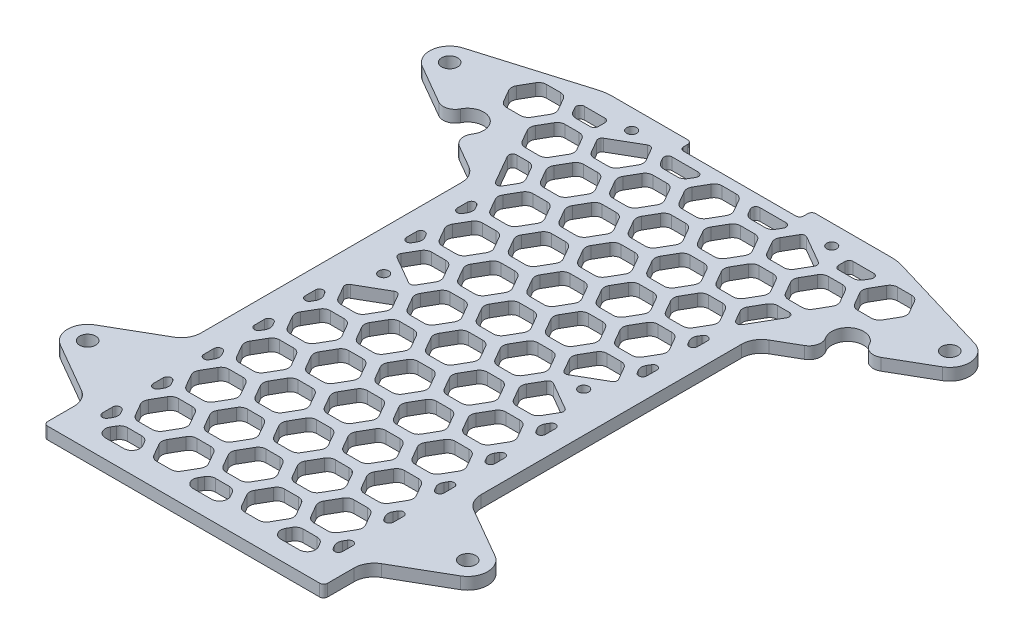
SolidWorks part; units mm, degrees
material "Thornel Mat VMA"
ref_plane "前视基准面" through (0, 0, 0) normal (0, 0, 1) x (1, 0, 0)
ref_plane "上视基准面" through (0, 0, 0) normal (0, 1, 0) x (1, 0, 0)
ref_plane "右视基准面" through (0, 0, 0) normal (1, 0, 0) x (0, 0, -1)
sketch "草图2" plane through (0, 0, 0) normal (0, 1, 0) x (1, 0, 0)
  line L0 (-43.1514, -24.9444) -> (-37.5, -28.2073)
  line L1 (35, -129.3771) -> (35, -137)
  line L3 (-47.5, -113.5) -> (-47.5, -18.5) construction
  line L6 (-37.8634, 4.5813) -> (-63.9317, -3.2094)
  line L7 (50, -117.8301) -> (37.5, -125.047)
  line L8 (37.5, -101.953) -> (50, -109.1699)
  line L11 (35, -32.5374) -> (35, -97.6229)
  line L14 (0, -55) -> (0, 55) construction
  line L16 (-35, 5) -> (35, 5)
  line L20 (43.1514, -24.9444) -> (37.5, -28.2073)
  line L23 (65, -12.3301) -> (55.2553, -17.9562)
  line L25 (-25, 0) -> (25, 0) construction
  line L26 (-25, 0) -> (-25, -62) construction
  line L27 (-25, -62) -> (25, -62) construction
  line L28 (25, 0) -> (25, -62) construction
  line L29 (-35, -129.3771) -> (-35, -137)
  line L30 (-35, -137) -> (35, -137)
  line L32 (-65, -12.3301) -> (-55.2553, -17.9562)
  line L33 (-35, -32.5374) -> (-35, -97.6229)
  line L34 (-37.5, -101.953) -> (-50, -109.1699)
  line L35 (-50, -117.8301) -> (-37.5, -125.047)
  line L36 (37.8634, 4.5813) -> (63.9317, -3.2094)
  arc A10 (-44.158, -20.6979) -> (-51.0745, -16.7047) centre (-47.5, -18.5) ccw
  circle A45 centre (-25, 0) radius 1.25
  circle A46 centre (-47.5, -43.5) radius 4 construction
  circle A47 centre (-62.5, -8) radius 2
  circle A49 centre (62.5, -8) radius 2
  circle A51 centre (47.5, -43.5) radius 4 construction
  circle A52 centre (25, 0) radius 1.25
  circle A53 centre (-25, -62) radius 1.25
  circle A54 centre (25, -62) radius 1.25
  arc A58 (-35, 5) -> (-37.8634, 4.5813) centre (-35, -5) ccw
  circle A59 centre (-47.5, -113.5) radius 2
  arc A60 (-50, -109.1699) -> (-50, -117.8301) centre (-47.5, -113.5) ccw
  arc A61 (-63.9317, -3.2094) -> (-65, -12.3301) centre (-62.5, -8) ccw
  arc A62 (-43.1514, -24.9444) -> (-44.158, -20.6979) centre (-41.6514, -22.3463) cw
  arc A63 (-51.0745, -16.7047) -> (-55.2553, -17.9562) centre (-53.7553, -15.3582) cw
  arc A64 (-35, -129.3771) -> (-37.5, -125.047) centre (-40, -129.3771) ccw
  arc A65 (-35, -97.6229) -> (-37.5, -101.953) centre (-40, -97.6229) cw
  arc A66 (-37.5, -28.2073) -> (-35, -32.5374) centre (-40, -32.5374) cw
  arc A67 (35, -129.3771) -> (37.5, -125.047) centre (40, -129.3771) cw
  circle A68 centre (47.5, -113.5) radius 2
  arc A69 (50, -109.1699) -> (50, -117.8301) centre (47.5, -113.5) cw
  arc A70 (35, -97.6229) -> (37.5, -101.953) centre (40, -97.6229) ccw
  arc A71 (37.5, -28.2073) -> (35, -32.5374) centre (40, -32.5374) ccw
  arc A72 (43.1514, -24.9444) -> (44.158, -20.6979) centre (41.6514, -22.3463) ccw
  arc A73 (44.158, -20.6979) -> (51.0745, -16.7047) centre (47.5, -18.5) cw
  arc A74 (51.0745, -16.7047) -> (55.2553, -17.9562) centre (53.7553, -15.3582) ccw
  arc A75 (63.9317, -3.2094) -> (65, -12.3301) centre (62.5, -8) cw
  arc A76 (35, 5) -> (37.8634, 4.5813) centre (35, -5) cw
  point P2 (36.4469, 55.8948)
  point P6 (0, 0)
  point P14 (-47.5, -63.0375)
  point P23 (0, 0)
  point P29 (-61.5336, 43)
  point P31 (-35, 38)
  point P32 (-35, 56)
  point P35 (-35.1257, 55.5775)
  point P36 (0, 0)
  point P37 (-47.5, 7.5)
  point P38 (-47.5, -61.5952)
  point P39 (32.0288, -82)
  point P41 (-35, -71.4625)
  point P42 (-35, 12.0845)
  point P44 (-35, 26.8228)
  dimension "D3" = 10
  dimension "D4" = 25
  dimension "D7" = 5
  dimension "D8" = 125
  dimension "D9" = 8
  dimension "D10" = 2.5
  dimension "D11" = 5
  dimension "D6" = 4
  dimension "D19" = 120
  dimension "D20" = 3
  dimension "D21" = 62
  dimension "D22" = 50
  dimension "D23" = 5
  dimension "D13" = 15
  dimension "D14" = 10.5
  dimension "D12" = 70
  dimension "D15" = 10
  dimension "D16" = 75
  dimension "D17" = 120
  dimension "D18" = 120
  dimension "D5" = 8
extrude "凸台-拉伸1" add sketch "草图2" along normal blind 3
sketch "草图5" plane through (0, 3, 0) normal (0, 1, 0) x (1, 0, 0)
  line L0 (2.8868, -10.6667) -> (2.8868, -13.3333) construction
  line L26 (-19.0526, -13.3333) -> (-24.8261, -13.3333)
  line L29 (-24.8261, -13.3333) -> (-27.7128, -18.3333)
  line L34 (-27.7128, -18.3333) -> (-24.8261, -23.3333)
  line L35 (-24.8261, -23.3333) -> (-19.0526, -23.3333)
  line L47 (35, 5) -> (-35, 5) construction
  line L60 (-19.0526, -23.3333) -> (-16.1658, -18.3333)
  line L61 (-16.1658, -18.3333) -> (-19.0526, -13.3333)
  line L65 (-30.0222, -19.6667) -> (-35.7957, -19.6667)
  line L104 (0, 0) -> (0, 5) construction
  line L105 (-25, 0) -> (25, -62) construction
  line L109 (-10.9697, -12) -> (-10.9697, -24.6667) construction
  line L113 (-15, 5) -> (15, 5)
  line L114 (-15, 5) -> (-15, 2)
  line L115 (-15, 2) -> (15, 2)
  line L116 (15, 5) -> (15, 2)
  line L122 (2.8868, -13.3333) -> (-2.8868, -13.3333)
  line L123 (-2.8868, -13.3333) -> (-5.7735, -18.3333)
  line L124 (-5.7735, -18.3333) -> (-2.8868, -23.3333)
  line L125 (-2.8868, -23.3333) -> (2.8868, -23.3333)
  line L126 (2.8868, -23.3333) -> (5.7735, -18.3333)
  line L127 (5.7735, -18.3333) -> (2.8868, -13.3333)
  line L128 (-8.0829, -19.6667) -> (-13.8564, -19.6667)
  line L129 (-13.8564, -19.6667) -> (-16.7432, -24.6667)
  line L130 (-16.7432, -24.6667) -> (-13.8564, -29.6667)
  line L131 (-13.8564, -29.6667) -> (-8.0829, -29.6667)
  line L132 (-8.0829, -29.6667) -> (-5.1962, -24.6667)
  line L133 (-5.1962, -24.6667) -> (-8.0829, -19.6667)
  line L134 (-8.0829, -7) -> (-13.8564, -7)
  line L135 (-13.8564, -7) -> (-16.7432, -12)
  line L136 (-16.7432, -12) -> (-13.8564, -17)
  line L137 (-13.8564, -17) -> (-8.0829, -17)
  line L138 (-8.0829, -17) -> (-5.1962, -12)
  line L139 (-5.1962, -12) -> (-8.0829, -7)
  line L140 (-10.9697, -24.6667) -> (0, -31) construction
  line L141 (0, -31) -> (0, -18.3333) construction
  line L142 (0, -18.3333) -> (-10.9697, -24.6667) construction
  line L143 (0, -5.6667) -> (0, -18.3333) construction
  line L144 (2.8868, -0.6667) -> (-2.8868, -0.6667)
  line L145 (-2.8868, -0.6667) -> (-5.7735, -5.6667)
  line L146 (-5.7735, -5.6667) -> (-2.8868, -10.6667)
  line L147 (-2.8868, -10.6667) -> (2.8868, -10.6667)
  line L148 (2.8868, -10.6667) -> (5.7735, -5.6667)
  line L149 (5.7735, -5.6667) -> (2.8868, -0.6667)
  line L151 (2.8868, -0.6667) -> (2.8868, 2) construction
  line L153 (-30.0222, -29.6667) -> (-27.1355, -24.6667)
  line L154 (-27.1355, -24.6667) -> (-30.0222, -19.6667)
  line L155 (-30.0222, -7) -> (-35.7957, -7)
  line L156 (-35.7957, -7) -> (-38.6825, -12)
  line L157 (-38.6825, -12) -> (-35.7957, -17)
  line L158 (-35.7957, -17) -> (-30.0222, -17)
  line L159 (-30.0222, -17) -> (-27.1355, -12)
  line L160 (-27.1355, -12) -> (-30.0222, -7)
  line L163 (-27.7128, -5.6667) -> (-24.8261, -10.6667)
  line L164 (-24.8261, -10.6667) -> (-19.0526, -10.6667)
  line L165 (-19.0526, -10.6667) -> (-16.1658, -5.6667)
  line L166 (-16.1658, -5.6667) -> (-19.0526, -0.6667)
  line L185 (-40.9919, -0.6667) -> (-46.7654, -0.6667)
  line L186 (-46.7654, -0.6667) -> (-49.6521, -5.6667)
  line L187 (-49.6521, -5.6667) -> (-46.7654, -10.6667)
  line L188 (-46.7654, -10.6667) -> (-40.9919, -10.6667)
  line L189 (-40.9919, -10.6667) -> (-38.1051, -5.6667)
  line L190 (-38.1051, -5.6667) -> (-40.9919, -0.6667)
  line L191 (-19.0526, -38.6667) -> (-24.8261, -38.6667)
  line L192 (-24.8261, -38.6667) -> (-27.7128, -43.6667)
  line L193 (-27.7128, -43.6667) -> (-24.8261, -48.6667)
  line L194 (-24.8261, -48.6667) -> (-19.0526, -48.6667)
  line L195 (-19.0526, -48.6667) -> (-16.1658, -43.6667)
  line L196 (-16.1658, -43.6667) -> (-19.0526, -38.6667)
  line L201 (-30.0222, -55) -> (-27.1355, -50)
  line L202 (-27.1355, -50) -> (-30.0222, -45)
  line L207 (-30.0222, -42.3333) -> (-27.1355, -37.3333)
  line L208 (-27.1355, -37.3333) -> (-30.0222, -32.3333)
  line L209 (-19.0526, -26) -> (-24.8261, -26)
  line L210 (-24.8261, -26) -> (-27.7128, -31)
  line L211 (-27.7128, -31) -> (-24.8261, -36)
  line L212 (-24.8261, -36) -> (-19.0526, -36)
  line L213 (-19.0526, -36) -> (-16.1658, -31)
  line L214 (-16.1658, -31) -> (-19.0526, -26)
  line L241 (-27.7128, -69) -> (-24.8261, -74)
  line L242 (-24.8261, -74) -> (-19.0526, -74)
  line L243 (-19.0526, -74) -> (-16.1658, -69)
  line L244 (-16.1658, -69) -> (-19.0526, -64)
  line L249 (-30.0222, -80.3333) -> (-27.1355, -75.3333)
  line L250 (-27.1355, -75.3333) -> (-30.0222, -70.3333)
  line L257 (-19.0526, -51.3333) -> (-24.8261, -51.3333)
  line L258 (-24.8261, -51.3333) -> (-27.7128, -56.3333)
  line L261 (-19.0526, -61.3333) -> (-16.1658, -56.3333)
  line L262 (-16.1658, -56.3333) -> (-19.0526, -51.3333)
  line L287 (-19.0526, -89.3333) -> (-24.8261, -89.3333)
  line L288 (-24.8261, -89.3333) -> (-27.7128, -94.3333)
  line L289 (-27.7128, -94.3333) -> (-24.8261, -99.3333)
  line L290 (-24.8261, -99.3333) -> (-19.0526, -99.3333)
  line L291 (-19.0526, -99.3333) -> (-16.1658, -94.3333)
  line L292 (-16.1658, -94.3333) -> (-19.0526, -89.3333)
  line L297 (-30.0222, -105.6667) -> (-27.1355, -100.6667)
  line L298 (-27.1355, -100.6667) -> (-30.0222, -95.6667)
  line L303 (-30.0222, -93) -> (-27.1355, -88)
  line L304 (-27.1355, -88) -> (-30.0222, -83)
  line L305 (-19.0526, -76.6667) -> (-24.8261, -76.6667)
  line L306 (-24.8261, -76.6667) -> (-27.7128, -81.6667)
  line L307 (-27.7128, -81.6667) -> (-24.8261, -86.6667)
  line L308 (-24.8261, -86.6667) -> (-19.0526, -86.6667)
  line L309 (-19.0526, -86.6667) -> (-16.1658, -81.6667)
  line L310 (-16.1658, -81.6667) -> (-19.0526, -76.6667)
  line L335 (-19.0526, -114.6667) -> (-24.8261, -114.6667)
  line L336 (-24.8261, -114.6667) -> (-27.7128, -119.6667)
  line L337 (-27.7128, -119.6667) -> (-24.8261, -124.6667)
  line L338 (-24.8261, -124.6667) -> (-19.0526, -124.6667)
  line L339 (-19.0526, -124.6667) -> (-16.1658, -119.6667)
  line L340 (-16.1658, -119.6667) -> (-19.0526, -114.6667)
  line L345 (-30.0222, -131) -> (-27.1355, -126)
  line L346 (-27.1355, -126) -> (-30.0222, -121)
  line L351 (-30.0222, -118.3333) -> (-27.1355, -113.3333)
  line L352 (-27.1355, -113.3333) -> (-30.0222, -108.3333)
  line L353 (-19.0526, -102) -> (-24.8261, -102)
  line L354 (-24.8261, -102) -> (-27.7128, -107)
  line L355 (-27.7128, -107) -> (-24.8261, -112)
  line L356 (-24.8261, -112) -> (-19.0526, -112)
  line L357 (-19.0526, -112) -> (-16.1658, -107)
  line L358 (-16.1658, -107) -> (-19.0526, -102)
  line L401 (-19.0526, -127.3333) -> (-24.8261, -127.3333)
  line L402 (-24.8261, -127.3333) -> (-27.7128, -132.3333)
  line L406 (-16.1658, -132.3333) -> (-19.0526, -127.3333)
  line L431 (2.8868, -38.6667) -> (-2.8868, -38.6667)
  line L432 (-2.8868, -38.6667) -> (-5.7735, -43.6667)
  line L433 (-5.7735, -43.6667) -> (-2.8868, -48.6667)
  line L434 (-2.8868, -48.6667) -> (2.8868, -48.6667)
  line L435 (2.8868, -48.6667) -> (5.7735, -43.6667)
  line L436 (5.7735, -43.6667) -> (2.8868, -38.6667)
  line L437 (-8.0829, -45) -> (-13.8564, -45)
  line L438 (-13.8564, -45) -> (-16.7432, -50)
  line L439 (-16.7432, -50) -> (-13.8564, -55)
  line L440 (-13.8564, -55) -> (-8.0829, -55)
  line L441 (-8.0829, -55) -> (-5.1962, -50)
  line L442 (-5.1962, -50) -> (-8.0829, -45)
  line L443 (-8.0829, -32.3333) -> (-13.8564, -32.3333)
  line L444 (-13.8564, -32.3333) -> (-16.7432, -37.3333)
  line L445 (-16.7432, -37.3333) -> (-13.8564, -42.3333)
  line L446 (-13.8564, -42.3333) -> (-8.0829, -42.3333)
  line L447 (-8.0829, -42.3333) -> (-5.1962, -37.3333)
  line L448 (-5.1962, -37.3333) -> (-8.0829, -32.3333)
  line L449 (2.8868, -26) -> (-2.8868, -26)
  line L450 (-2.8868, -26) -> (-5.7735, -31)
  line L451 (-5.7735, -31) -> (-2.8868, -36)
  line L452 (-2.8868, -36) -> (2.8868, -36)
  line L453 (2.8868, -36) -> (5.7735, -31)
  line L454 (5.7735, -31) -> (2.8868, -26)
  line L455 (2.8868, -64) -> (-2.8868, -64)
  line L456 (-2.8868, -64) -> (-5.7735, -69)
  line L457 (-5.7735, -69) -> (-2.8868, -74)
  line L458 (-2.8868, -74) -> (2.8868, -74)
  line L459 (2.8868, -74) -> (5.7735, -69)
  line L460 (5.7735, -69) -> (2.8868, -64)
  line L461 (-8.0829, -70.3333) -> (-13.8564, -70.3333)
  line L462 (-13.8564, -70.3333) -> (-16.7432, -75.3333)
  line L463 (-16.7432, -75.3333) -> (-13.8564, -80.3333)
  line L464 (-13.8564, -80.3333) -> (-8.0829, -80.3333)
  line L465 (-8.0829, -80.3333) -> (-5.1962, -75.3333)
  line L466 (-5.1962, -75.3333) -> (-8.0829, -70.3333)
  line L467 (-8.0829, -57.6667) -> (-13.8564, -57.6667)
  line L468 (-13.8564, -57.6667) -> (-16.7432, -62.6667)
  line L469 (-16.7432, -62.6667) -> (-13.8564, -67.6667)
  line L470 (-13.8564, -67.6667) -> (-8.0829, -67.6667)
  line L471 (-8.0829, -67.6667) -> (-5.1962, -62.6667)
  line L472 (-5.1962, -62.6667) -> (-8.0829, -57.6667)
  line L473 (2.8868, -51.3333) -> (-2.8868, -51.3333)
  line L474 (-2.8868, -51.3333) -> (-5.7735, -56.3333)
  line L475 (-5.7735, -56.3333) -> (-2.8868, -61.3333)
  line L476 (-2.8868, -61.3333) -> (2.8868, -61.3333)
  line L477 (2.8868, -61.3333) -> (5.7735, -56.3333)
  line L478 (5.7735, -56.3333) -> (2.8868, -51.3333)
  line L479 (2.8868, -89.3333) -> (-2.8868, -89.3333)
  line L480 (-2.8868, -89.3333) -> (-5.7735, -94.3333)
  line L481 (-5.7735, -94.3333) -> (-2.8868, -99.3333)
  line L482 (-2.8868, -99.3333) -> (2.8868, -99.3333)
  line L483 (2.8868, -99.3333) -> (5.7735, -94.3333)
  line L484 (5.7735, -94.3333) -> (2.8868, -89.3333)
  line L485 (-8.0829, -95.6667) -> (-13.8564, -95.6667)
  line L486 (-13.8564, -95.6667) -> (-16.7432, -100.6667)
  line L487 (-16.7432, -100.6667) -> (-13.8564, -105.6667)
  line L488 (-13.8564, -105.6667) -> (-8.0829, -105.6667)
  line L489 (-8.0829, -105.6667) -> (-5.1962, -100.6667)
  line L490 (-5.1962, -100.6667) -> (-8.0829, -95.6667)
  line L491 (-8.0829, -83) -> (-13.8564, -83)
  line L492 (-13.8564, -83) -> (-16.7432, -88)
  line L493 (-16.7432, -88) -> (-13.8564, -93)
  line L494 (-13.8564, -93) -> (-8.0829, -93)
  line L495 (-8.0829, -93) -> (-5.1962, -88)
  line L496 (-5.1962, -88) -> (-8.0829, -83)
  line L497 (2.8868, -76.6667) -> (-2.8868, -76.6667)
  line L498 (-2.8868, -76.6667) -> (-5.7735, -81.6667)
  line L499 (-5.7735, -81.6667) -> (-2.8868, -86.6667)
  line L500 (-2.8868, -86.6667) -> (2.8868, -86.6667)
  line L501 (2.8868, -86.6667) -> (5.7735, -81.6667)
  line L502 (5.7735, -81.6667) -> (2.8868, -76.6667)
  line L503 (2.8868, -114.6667) -> (-2.8868, -114.6667)
  line L504 (-2.8868, -114.6667) -> (-5.7735, -119.6667)
  line L505 (-5.7735, -119.6667) -> (-2.8868, -124.6667)
  line L506 (-2.8868, -124.6667) -> (2.8868, -124.6667)
  line L507 (2.8868, -124.6667) -> (5.7735, -119.6667)
  line L508 (5.7735, -119.6667) -> (2.8868, -114.6667)
  line L509 (-8.0829, -121) -> (-13.8564, -121)
  line L510 (-13.8564, -121) -> (-16.7432, -126)
  line L511 (-16.7432, -126) -> (-13.8564, -131)
  line L512 (-13.8564, -131) -> (-8.0829, -131)
  line L513 (-8.0829, -131) -> (-5.1962, -126)
  line L514 (-5.1962, -126) -> (-8.0829, -121)
  line L515 (-8.0829, -108.3333) -> (-13.8564, -108.3333)
  line L516 (-13.8564, -108.3333) -> (-16.7432, -113.3333)
  line L517 (-16.7432, -113.3333) -> (-13.8564, -118.3333)
  line L518 (-13.8564, -118.3333) -> (-8.0829, -118.3333)
  line L519 (-8.0829, -118.3333) -> (-5.1962, -113.3333)
  line L520 (-5.1962, -113.3333) -> (-8.0829, -108.3333)
  line L521 (2.8868, -102) -> (-2.8868, -102)
  line L522 (-2.8868, -102) -> (-5.7735, -107)
  line L523 (-5.7735, -107) -> (-2.8868, -112)
  line L524 (-2.8868, -112) -> (2.8868, -112)
  line L525 (2.8868, -112) -> (5.7735, -107)
  line L526 (5.7735, -107) -> (2.8868, -102)
  line L545 (2.8868, -127.3333) -> (-2.8868, -127.3333)
  line L546 (-2.8868, -127.3333) -> (-5.7735, -132.3333)
  line L550 (5.7735, -132.3333) -> (2.8868, -127.3333)
  line L551 (-10.9697, -12) -> (-21.9393, -18.3333) construction
  line L552 (-21.9393, -18.3333) -> (-10.9697, -24.6667) construction
  line L553 (-19.0526, -0.6667) -> (-27.7128, -5.6667)
  line L554 (-57.735, -55) -> (-51.9615, -55)
  line L555 (-40.9919, -64) -> (-46.7654, -64)
  line L556 (-46.7654, -64) -> (-49.6521, -69)
  line L557 (-49.6521, -69) -> (-46.7654, -74)
  line L558 (-46.7654, -74) -> (-40.9919, -74)
  line L559 (-40.9919, -74) -> (-38.1051, -69)
  line L560 (-38.1051, -69) -> (-40.9919, -64)
  line L561 (-51.9615, -70.3333) -> (-57.735, -70.3333)
  line L562 (-57.735, -70.3333) -> (-60.6218, -75.3333)
  line L563 (-60.6218, -75.3333) -> (-57.735, -80.3333)
  line L564 (-57.735, -80.3333) -> (-51.9615, -80.3333)
  line L565 (-51.9615, -80.3333) -> (-49.0748, -75.3333)
  line L566 (-49.0748, -75.3333) -> (-51.9615, -70.3333)
  line L567 (-51.9615, -57.6667) -> (-57.735, -57.6667)
  line L568 (-57.735, -57.6667) -> (-60.6218, -62.6667)
  line L569 (-60.6218, -62.6667) -> (-57.735, -67.6667)
  line L570 (-57.735, -67.6667) -> (-51.9615, -67.6667)
  line L571 (-51.9615, -67.6667) -> (-49.0748, -62.6667)
  line L572 (-49.0748, -62.6667) -> (-51.9615, -57.6667)
  line L573 (-49.6521, -56.3333) -> (-46.7654, -61.3333)
  line L574 (-46.7654, -61.3333) -> (-40.9919, -61.3333)
  line L575 (-40.9919, -61.3333) -> (-38.1051, -56.3333)
  line L576 (-40.9919, -89.3333) -> (-46.7654, -89.3333)
  line L577 (-46.7654, -89.3333) -> (-49.6521, -94.3333)
  line L578 (-49.6521, -94.3333) -> (-46.7654, -99.3333)
  line L579 (-46.7654, -99.3333) -> (-40.9919, -99.3333)
  line L580 (-40.9919, -99.3333) -> (-38.1051, -94.3333)
  line L581 (-38.1051, -94.3333) -> (-40.9919, -89.3333)
  line L582 (-51.9615, -95.6667) -> (-57.735, -95.6667)
  line L583 (-57.735, -95.6667) -> (-60.6218, -100.6667)
  line L584 (-60.6218, -100.6667) -> (-57.735, -105.6667)
  line L585 (-57.735, -105.6667) -> (-51.9615, -105.6667)
  line L586 (-51.9615, -105.6667) -> (-49.0748, -100.6667)
  line L587 (-49.0748, -100.6667) -> (-51.9615, -95.6667)
  line L588 (-51.9615, -83) -> (-57.735, -83)
  line L589 (-57.735, -83) -> (-60.6218, -88)
  line L590 (-60.6218, -88) -> (-57.735, -93)
  line L591 (-57.735, -93) -> (-51.9615, -93)
  line L592 (-51.9615, -93) -> (-49.0748, -88)
  line L593 (-49.0748, -88) -> (-51.9615, -83)
  line L594 (-40.9919, -76.6667) -> (-46.7654, -76.6667)
  line L595 (-46.7654, -76.6667) -> (-49.6521, -81.6667)
  line L596 (-49.6521, -81.6667) -> (-46.7654, -86.6667)
  line L597 (-46.7654, -86.6667) -> (-40.9919, -86.6667)
  line L598 (-40.9919, -86.6667) -> (-38.1051, -81.6667)
  line L599 (-38.1051, -81.6667) -> (-40.9919, -76.6667)
  line L600 (-40.9919, -114.6667) -> (-46.7654, -114.6667)
  line L601 (-46.7654, -114.6667) -> (-49.6521, -119.6667)
  line L602 (-49.6521, -119.6667) -> (-46.7654, -124.6667)
  line L603 (-46.7654, -124.6667) -> (-40.9919, -124.6667)
  line L604 (-40.9919, -124.6667) -> (-38.1051, -119.6667)
  line L605 (-38.1051, -119.6667) -> (-40.9919, -114.6667)
  line L606 (-51.9615, -121) -> (-57.735, -121)
  line L607 (-57.735, -121) -> (-60.6218, -126)
  line L608 (-60.6218, -126) -> (-57.735, -131)
  line L609 (-57.735, -131) -> (-51.9615, -131)
  line L610 (-51.9615, -131) -> (-49.0748, -126)
  line L611 (-49.0748, -126) -> (-51.9615, -121)
  line L612 (-51.9615, -108.3333) -> (-57.735, -108.3333)
  line L613 (-57.735, -108.3333) -> (-60.6218, -113.3333)
  line L614 (-60.6218, -113.3333) -> (-57.735, -118.3333)
  line L615 (-57.735, -118.3333) -> (-51.9615, -118.3333)
  line L616 (-51.9615, -118.3333) -> (-49.0748, -113.3333)
  line L617 (-49.0748, -113.3333) -> (-51.9615, -108.3333)
  line L618 (-40.9919, -102) -> (-46.7654, -102)
  line L619 (-46.7654, -102) -> (-49.6521, -107)
  line L620 (-49.6521, -107) -> (-46.7654, -112)
  line L621 (-46.7654, -112) -> (-40.9919, -112)
  line L622 (-40.9919, -112) -> (-38.1051, -107)
  line L623 (-38.1051, -107) -> (-40.9919, -102)
  line L624 (-40.9919, -140) -> (-46.7654, -140)
  line L625 (-46.7654, -140) -> (-49.6521, -145)
  line L626 (-49.6521, -145) -> (-46.7654, -150)
  line L627 (-46.7654, -150) -> (-40.9919, -150)
  line L628 (-40.9919, -150) -> (-38.1051, -145)
  line L629 (-38.1051, -145) -> (-40.9919, -140)
  line L630 (-51.9615, -146.3333) -> (-57.735, -146.3333)
  line L631 (-57.735, -146.3333) -> (-60.6218, -151.3333)
  line L632 (-60.6218, -151.3333) -> (-57.735, -156.3333)
  line L633 (-57.735, -156.3333) -> (-51.9615, -156.3333)
  line L634 (-51.9615, -156.3333) -> (-49.0748, -151.3333)
  line L635 (-49.0748, -151.3333) -> (-51.9615, -146.3333)
  line L636 (-51.9615, -133.6667) -> (-57.735, -133.6667)
  line L637 (-57.735, -133.6667) -> (-60.6218, -138.6667)
  line L638 (-60.6218, -138.6667) -> (-57.735, -143.6667)
  line L639 (-57.735, -143.6667) -> (-51.9615, -143.6667)
  line L640 (-51.9615, -143.6667) -> (-49.0748, -138.6667)
  line L641 (-49.0748, -138.6667) -> (-51.9615, -133.6667)
  line L642 (-40.9919, -127.3333) -> (-46.7654, -127.3333)
  line L643 (-46.7654, -127.3333) -> (-49.6521, -132.3333)
  line L644 (-49.6521, -132.3333) -> (-46.7654, -137.3333)
  line L645 (-46.7654, -137.3333) -> (-40.9919, -137.3333)
  line L646 (-40.9919, -137.3333) -> (-38.1051, -132.3333)
  line L647 (-38.1051, -132.3333) -> (-40.9919, -127.3333)
  line L648 (-40.9919, -13.3333) -> (-46.7654, -13.3333)
  line L649 (-46.7654, -13.3333) -> (-49.6521, -18.3333)
  line L650 (-49.6521, -18.3333) -> (-46.7654, -23.3333)
  line L651 (-46.7654, -23.3333) -> (-40.9919, -23.3333)
  line L652 (-40.9919, -23.3333) -> (-38.1051, -18.3333)
  line L653 (-38.1051, -18.3333) -> (-40.9919, -13.3333)
  line L654 (-51.9615, -19.6667) -> (-57.735, -19.6667)
  line L655 (-57.735, -19.6667) -> (-60.6218, -24.6667)
  line L656 (-60.6218, -24.6667) -> (-57.735, -29.6667)
  line L657 (-57.735, -29.6667) -> (-51.9615, -29.6667)
  line L658 (-51.9615, -29.6667) -> (-49.0748, -24.6667)
  line L659 (-49.0748, -24.6667) -> (-51.9615, -19.6667)
  line L660 (-60.6218, -12) -> (-57.735, -17)
  line L661 (-57.735, -17) -> (-51.9615, -17)
  line L662 (-51.9615, -17) -> (-49.0748, -12)
  line L663 (-40.9919, -38.6667) -> (-46.7654, -38.6667)
  line L664 (-46.7654, -38.6667) -> (-49.6521, -43.6667)
  line L665 (-49.6521, -43.6667) -> (-46.7654, -48.6667)
  line L666 (-46.7654, -48.6667) -> (-40.9919, -48.6667)
  line L667 (-40.9919, -48.6667) -> (-38.1051, -43.6667)
  line L668 (-38.1051, -43.6667) -> (-40.9919, -38.6667)
  line L669 (-51.9615, -45) -> (-57.735, -45)
  line L670 (-57.735, -45) -> (-60.6218, -50)
  line L671 (-60.6218, -50) -> (-57.735, -55)
  line L672 (-51.9615, -55) -> (-49.0748, -50)
  line L673 (-49.0748, -50) -> (-51.9615, -45)
  line L674 (-51.9615, -32.3333) -> (-57.735, -32.3333)
  line L675 (-57.735, -32.3333) -> (-60.6218, -37.3333)
  line L676 (-60.6218, -37.3333) -> (-57.735, -42.3333)
  line L677 (-57.735, -42.3333) -> (-51.9615, -42.3333)
  line L678 (-51.9615, -42.3333) -> (-49.0748, -37.3333)
  line L679 (-49.0748, -37.3333) -> (-51.9615, -32.3333)
  line L680 (-40.9919, -26) -> (-46.7654, -26)
  line L681 (-46.7654, -26) -> (-49.6521, -31)
  line L682 (-49.6521, -31) -> (-46.7654, -36)
  line L683 (-46.7654, -36) -> (-40.9919, -36)
  line L684 (-40.9919, -36) -> (-38.1051, -31)
  line L685 (-38.1051, -31) -> (-40.9919, -26)
  line L686 (-40.9919, -51.3333) -> (-46.7654, -51.3333)
  line L687 (-46.7654, -51.3333) -> (-49.6521, -56.3333)
  line L688 (-38.1051, -56.3333) -> (-40.9919, -51.3333)
  line L689 (-51.9615, -7) -> (-57.735, -7)
  line L690 (-57.735, -7) -> (-60.6218, -12)
  line L691 (-49.0748, -12) -> (-51.9615, -7)
  line L692 (-15.9734, -0.6667) -> (-13.8564, -4.3333)
  line L693 (-13.8564, -4.3333) -> (-8.0829, -4.3333)
  line L694 (-8.0829, -4.3333) -> (-5.966, -0.6667)
  line L695 (-5.966, -0.6667) -> (-15.9734, -0.6667)
  line L696 (-8.0829, -4.3333) -> (-8.0829, -7) construction
  line L697 (-35.7957, -7) -> (-35.7957, -4.3333) construction
  line L698 (-19.0526, -0.6667) -> (-24.8261, -0.6667)
  line L699 (-24.8261, -0.6667) -> (-27.7128, -5.6667)
  line L700 (-37.9127, -0.6667) -> (-30.0222, -0.6667)
  line L701 (-37.9127, -0.6667) -> (-35.7957, -4.3333)
  line L702 (-35.7957, -4.3333) -> (-30.0222, -4.3333)
  line L703 (-30.0222, -0.6667) -> (-30.0222, -4.3333)
  line L704 (-35.7957, -19.6667) -> (-30.0222, -29.6667)
  line L705 (-35.7957, -19.6667) -> (-38.6825, -24.6667)
  line L706 (-38.6825, -24.6667) -> (-35.7957, -29.6667)
  line L707 (-35.7957, -29.6667) -> (-30.0222, -29.6667)
  line L708 (-30.0222, -45) -> (-35.7957, -45)
  line L709 (-35.7957, -45) -> (-38.6825, -50)
  line L710 (-38.6825, -50) -> (-35.7957, -55)
  line L711 (-35.7957, -55) -> (-30.0222, -55)
  line L712 (-30.0222, -32.3333) -> (-35.7957, -32.3333)
  line L713 (-35.7957, -32.3333) -> (-38.6825, -37.3333)
  line L714 (-38.6825, -37.3333) -> (-35.7957, -42.3333)
  line L715 (-35.7957, -42.3333) -> (-30.0222, -42.3333)
  line L716 (-30.0222, -70.3333) -> (-35.7957, -70.3333)
  line L717 (-35.7957, -70.3333) -> (-38.6825, -75.3333)
  line L718 (-38.6825, -75.3333) -> (-35.7957, -80.3333)
  line L719 (-35.7957, -80.3333) -> (-30.0222, -80.3333)
  line L720 (-30.0222, -57.6667) -> (-35.7957, -57.6667)
  line L721 (-35.7957, -57.6667) -> (-38.6825, -62.6667)
  line L722 (-38.6825, -62.6667) -> (-35.7957, -67.6667)
  line L723 (-35.7957, -67.6667) -> (-30.0222, -67.6667)
  line L724 (-30.0222, -95.6667) -> (-35.7957, -95.6667)
  line L725 (-35.7957, -95.6667) -> (-38.6825, -100.6667)
  line L726 (-38.6825, -100.6667) -> (-35.7957, -105.6667)
  line L727 (-35.7957, -105.6667) -> (-30.0222, -105.6667)
  line L728 (-30.0222, -83) -> (-35.7957, -83)
  line L729 (-35.7957, -83) -> (-38.6825, -88)
  line L730 (-38.6825, -88) -> (-35.7957, -93)
  line L731 (-35.7957, -93) -> (-30.0222, -93)
  line L732 (-30.0222, -121) -> (-35.7957, -121)
  line L733 (-35.7957, -121) -> (-38.6825, -126)
  line L734 (-38.6825, -126) -> (-35.7957, -131)
  line L735 (-35.7957, -131) -> (-30.0222, -131)
  line L736 (-30.0222, -108.3333) -> (-35.7957, -108.3333)
  line L737 (-35.7957, -108.3333) -> (-38.6825, -113.3333)
  line L738 (-38.6825, -113.3333) -> (-35.7957, -118.3333)
  line L739 (-35.7957, -118.3333) -> (-30.0222, -118.3333)
  line L740 (-30.0222, -146.3333) -> (-35.7957, -146.3333)
  line L741 (-35.7957, -146.3333) -> (-38.6825, -151.3333)
  line L742 (-38.6825, -151.3333) -> (-35.7957, -156.3333)
  line L743 (-35.7957, -156.3333) -> (-30.0222, -156.3333)
  line L744 (-30.0222, -133.6667) -> (-35.7957, -133.6667)
  line L745 (-35.7957, -133.6667) -> (-38.6825, -138.6667)
  line L746 (-38.6825, -138.6667) -> (-35.7957, -143.6667)
  line L747 (-35.7957, -143.6667) -> (-30.0222, -143.6667)
  line L748 (-19.0526, -140) -> (-24.8261, -140)
  line L749 (-24.8261, -140) -> (-27.7128, -145)
  line L750 (-27.7128, -145) -> (-24.8261, -150)
  line L751 (-24.8261, -150) -> (-19.0526, -150)
  line L752 (-19.0526, -150) -> (-16.1658, -145)
  line L753 (-16.1658, -145) -> (-19.0526, -140)
  line L754 (-30.0222, -156.3333) -> (-27.1355, -151.3333)
  line L755 (-27.1355, -151.3333) -> (-30.0222, -146.3333)
  line L756 (-30.0222, -143.6667) -> (-27.1355, -138.6667)
  line L757 (-27.1355, -138.6667) -> (-30.0222, -133.6667)
  line L758 (-27.7128, -132.3333) -> (-24.8261, -137.3333)
  line L759 (-24.8261, -137.3333) -> (-19.0526, -137.3333)
  line L760 (-19.0526, -137.3333) -> (-16.1658, -132.3333)
  line L761 (2.8868, -140) -> (-2.8868, -140)
  line L762 (-2.8868, -140) -> (-5.7735, -145)
  line L763 (-5.7735, -145) -> (-2.8868, -150)
  line L764 (-2.8868, -150) -> (2.8868, -150)
  line L765 (2.8868, -150) -> (5.7735, -145)
  line L766 (5.7735, -145) -> (2.8868, -140)
  line L767 (-8.0829, -146.3333) -> (-13.8564, -146.3333)
  line L768 (-13.8564, -146.3333) -> (-16.7432, -151.3333)
  line L769 (-16.7432, -151.3333) -> (-13.8564, -156.3333)
  line L770 (-13.8564, -156.3333) -> (-8.0829, -156.3333)
  line L771 (-8.0829, -156.3333) -> (-5.1962, -151.3333)
  line L772 (-5.1962, -151.3333) -> (-8.0829, -146.3333)
  line L773 (-13.8564, -133.6667) -> (-16.7432, -138.6667)
  line L774 (-16.7432, -138.6667) -> (-13.8564, -143.6667)
  line L775 (-13.8564, -143.6667) -> (-8.0829, -143.6667)
  line L776 (-8.0829, -143.6667) -> (-5.1962, -138.6667)
  line L777 (-5.1962, -138.6667) -> (-8.0829, -133.6667)
  line L778 (-5.7735, -132.3333) -> (-2.8868, -137.3333)
  line L779 (-2.8868, -137.3333) -> (2.8868, -137.3333)
  line L780 (2.8868, -137.3333) -> (5.7735, -132.3333)
  line L781 (-8.0829, -133.6667) -> (-13.8564, -133.6667)
  line L782 (-30.0222, -32.3333) -> (-30.0222, -42.3333)
  line L783 (-30.0222, -55) -> (-30.0222, -45)
  line L785 (-30.0222, -70.3333) -> (-30.0222, -80.3333)
  line L786 (-30.0222, -83) -> (-30.0222, -93)
  line L787 (-30.0222, -95.6667) -> (-30.0222, -105.6667)
  line L788 (-30.0222, -108.3333) -> (-30.0222, -118.3333)
  line L789 (-30.0222, -121) -> (-30.0222, -131)
  line L790 (-27.7128, -132.3333) -> (-16.1658, -132.3333)
  line L791 (-19.0526, -61.3333) -> (-27.7128, -56.3333)
  line L792 (-27.7128, -69) -> (-19.0526, -64)
  line L794 (5.7735, -132.3333) -> (-5.7735, -132.3333)
  line L796 (-24.8261, -61.3333) -> (-19.0526, -61.3333)
  line L797 (-27.7128, -56.3333) -> (-24.8261, -61.3333)
  line L798 (-19.0526, -64) -> (-24.8261, -64)
  line L799 (-24.8261, -64) -> (-27.7128, -69)
  line L800 (-30.0222, -67.6667) -> (-27.1355, -62.6667)
  line L801 (-27.1355, -62.6667) -> (-30.0222, -57.6667)
  circle A20 centre (0, -31) radius 5 construction
  circle A21 centre (-21.9393, -18.3333) radius 5 construction
  circle A22 centre (0, -18.3333) radius 5 construction
  circle A23 centre (-10.9697, -24.6667) radius 5 construction
  circle A24 centre (-10.9697, -12) radius 5 construction
  circle A25 centre (0, -5.6667) radius 5 construction
  dimension "D3" = 10
  dimension "D4" = 6
  dimension "D1" = 3
  dimension "D2" = 30
  dimension "D5" = 3
extrude "切除-拉伸4" cut sketch "草图5" against normal through all
mirror "镜向1" about plane through (0, 0, 0) normal (1, 0, 0) of "切除-拉伸4"
fillet "圆角2" radius 1 60 edges at (30.0222, 1.5, 32.3333) (30.0222, 1.5, 45) (30.0222, 1.5, 70.3333) (30.0222, 1.5, 83) (30.0222, 1.5, 95.6667) (30.0222, 1.5, 108.3333) (30.0222, 1.5, 121) (30.0222, 1.5, 131) (30.0222, 1.5, 118.3333) (30.0222, 1.5, 105.6667) (30.0222, 1.5, 93) (30.0222, 1.5, 80.3333) (30.0222, 1.5, 55) (30.0222, 1.5, 42.3333) (-30.0222, 1.5, 42.3333) (-30.0222, 1.5, 55) (-30.0222, 1.5, 80.3333) (-30.0222, 1.5, 93) (-30.0222, 1.5, 105.6667) (-30.0222, 1.5, 118.3333) (-30.0222, 1.5, 131) (-30.0222, 1.5, 121) (-30.0222, 1.5, 108.3333) (-30.0222, 1.5, 95.6667) (-30.0222, 1.5, 83) (-30.0222, 1.5, 70.3333) (-30.0222, 1.5, 45) (-30.0222, 1.5, 32.3333) (35.7957, 1.5, 19.6667) (30.0222, 1.5, 29.6667) (-35.7957, 1.5, 19.6667) (-30.0222, 1.5, 29.6667) (30.0222, 1.5, 4.3333) (37.9127, 1.5, 0.6667) (30.0222, 1.5, 0.6667) (27.7128, 1.5, 5.6667) (19.0526, 1.5, 0.6667) (15.9734, 1.5, 0.6667) (5.966, 1.5, 0.6667) (-5.966, 1.5, 0.6667) (-15.9734, 1.5, 0.6667) (-19.0526, 1.5, 0.6667) (-27.7128, 1.5, 5.6667) (-30.0222, 1.5, 4.3333) (-30.0222, 1.5, 0.6667) (-37.9127, 1.5, 0.6667) (35, 1.5, 137) (-35, 1.5, 137) (15, 1.5, -5) (15, 1.5, -2) (-15, 1.5, -2) (-15, 1.5, -5) (19.0526, 1.5, 61.3333) (27.7128, 1.5, 56.3333) (27.7128, 1.5, 69) (19.0526, 1.5, 64) (-27.7128, 1.5, 69) (-19.0526, 1.5, 64) (-27.7128, 1.5, 56.3333) (-19.0526, 1.5, 61.3333)
fillet "圆角1" radius 2 342 edges at (16.1658, 1.5, 119.6667) (19.0526, 1.5, 114.6667) (24.8261, 1.5, 114.6667) (27.7128, 1.5, 119.6667) (24.8261, 1.5, 124.6667) (19.0526, 1.5, 124.6667) (27.1355, 1.5, 126) (27.1355, 1.5, 88) (16.1658, 1.5, 81.6667) (19.0526, 1.5, 76.6667) (24.8261, 1.5, 76.6667) (27.7128, 1.5, 81.6667) (24.8261, 1.5, 86.6667) (19.0526, 1.5, 86.6667) (16.1658, 1.5, 94.3333) (19.0526, 1.5, 89.3333) (24.8261, 1.5, 89.3333) (27.7128, 1.5, 94.3333) (24.8261, 1.5, 99.3333) (19.0526, 1.5, 99.3333) (27.1355, 1.5, 100.6667) (16.1658, 1.5, 56.3333) (19.0526, 1.5, 51.3333) (24.8261, 1.5, 51.3333) (27.1355, 1.5, 75.3333) (5.1962, 1.5, 50) (8.0829, 1.5, 45) (13.8564, 1.5, 45) (16.7432, 1.5, 50) (13.8564, 1.5, 55) (8.0829, 1.5, 55) (5.1962, 1.5, 37.3333) (8.0829, 1.5, 32.3333) (13.8564, 1.5, 32.3333) (16.7432, 1.5, 37.3333) (13.8564, 1.5, 42.3333) (8.0829, 1.5, 42.3333) (16.1658, 1.5, 107) (19.0526, 1.5, 102) (24.8261, 1.5, 102) (27.7128, 1.5, 107) (24.8261, 1.5, 112) (19.0526, 1.5, 112) (27.1355, 1.5, 113.3333) (16.1658, 1.5, 132.3333) (19.0526, 1.5, 127.3333) (24.8261, 1.5, 127.3333) (27.7128, 1.5, 132.3333) (27.1355, 1.5, 12) (30.0222, 1.5, 7) (35.7957, 1.5, 7) (38.6825, 1.5, 12) (35.7957, 1.5, 17) (30.0222, 1.5, 17) (27.1355, 1.5, 24.6667) (30.0222, 1.5, 19.6667) (5.1962, 1.5, 12) (8.0829, 1.5, 7) (13.8564, 1.5, 7) (16.7432, 1.5, 12) (13.8564, 1.5, 17) (8.0829, 1.5, 17) (16.1658, 1.5, 18.3333) (19.0526, 1.5, 13.3333) (24.8261, 1.5, 13.3333) (27.7128, 1.5, 18.3333) (24.8261, 1.5, 23.3333) (19.0526, 1.5, 23.3333) (5.1962, 1.5, 24.6667) (8.0829, 1.5, 19.6667) (13.8564, 1.5, 19.6667) (16.7432, 1.5, 24.6667) (13.8564, 1.5, 29.6667) (8.0829, 1.5, 29.6667) (27.1355, 1.5, 50) (27.1355, 1.5, 37.3333) (16.1658, 1.5, 31) (19.0526, 1.5, 26) (24.8261, 1.5, 26) (27.7128, 1.5, 31) (24.8261, 1.5, 36) (19.0526, 1.5, 36) (24.8261, 1.5, 74) (19.0526, 1.5, 74) (16.1658, 1.5, 69) (24.8261, 1.5, 10.6667) (19.0526, 1.5, 10.6667) (16.1658, 1.5, 5.6667) (35.7957, 1.5, 4.3333) (38.1051, 1.5, 5.6667) (40.9919, 1.5, 0.6667) (46.7654, 1.5, 0.6667) (49.6521, 1.5, 5.6667) (46.7654, 1.5, 10.6667) (40.9919, 1.5, 10.6667) (16.1658, 1.5, 43.6667) (19.0526, 1.5, 38.6667) (24.8261, 1.5, 38.6667) (27.7128, 1.5, 43.6667) (24.8261, 1.5, 48.6667) (19.0526, 1.5, 48.6667) (5.1962, 1.5, 126) (8.0829, 1.5, 121) (13.8564, 1.5, 121) (16.7432, 1.5, 126) (13.8564, 1.5, 131) (8.0829, 1.5, 131) (5.1962, 1.5, 113.3333) (8.0829, 1.5, 108.3333) (13.8564, 1.5, 108.3333) (16.7432, 1.5, 113.3333) (13.8564, 1.5, 118.3333) (8.0829, 1.5, 118.3333) (5.1962, 1.5, 62.6667) (8.0829, 1.5, 57.6667) (13.8564, 1.5, 57.6667) (16.7432, 1.5, 62.6667) (13.8564, 1.5, 67.6667) (8.0829, 1.5, 67.6667) (5.1962, 1.5, 75.3333) (8.0829, 1.5, 70.3333) (13.8564, 1.5, 70.3333) (16.7432, 1.5, 75.3333) (13.8564, 1.5, 80.3333) (8.0829, 1.5, 80.3333) (5.1962, 1.5, 88) (8.0829, 1.5, 83) (13.8564, 1.5, 83) (16.7432, 1.5, 88) (13.8564, 1.5, 93) (8.0829, 1.5, 93) (5.1962, 1.5, 100.6667) (8.0829, 1.5, 95.6667) (13.8564, 1.5, 95.6667) (16.7432, 1.5, 100.6667) (13.8564, 1.5, 105.6667) (8.0829, 1.5, 105.6667) (13.8564, 1.5, 4.3333) (8.0829, 1.5, 4.3333) (-19.0526, 1.5, 114.6667) (-16.1658, 1.5, 119.6667) (-19.0526, 1.5, 124.6667) (-24.8261, 1.5, 124.6667) (-27.7128, 1.5, 119.6667) (-24.8261, 1.5, 114.6667) (-27.1355, 1.5, 126) (-27.1355, 1.5, 88) (-19.0526, 1.5, 76.6667) (-16.1658, 1.5, 81.6667) (-19.0526, 1.5, 86.6667) (-24.8261, 1.5, 86.6667) (-27.7128, 1.5, 81.6667) (-24.8261, 1.5, 76.6667) (-19.0526, 1.5, 89.3333) (-16.1658, 1.5, 94.3333) (-19.0526, 1.5, 99.3333) (-24.8261, 1.5, 99.3333) (-27.7128, 1.5, 94.3333) (-24.8261, 1.5, 89.3333) (-27.1355, 1.5, 100.6667) (-19.0526, 1.5, 51.3333) (-16.1658, 1.5, 56.3333) (-24.8261, 1.5, 51.3333) (-27.1355, 1.5, 75.3333) (-8.0829, 1.5, 45) (-5.1962, 1.5, 50) (-8.0829, 1.5, 55) (-13.8564, 1.5, 55) (-16.7432, 1.5, 50) (-13.8564, 1.5, 45) (-8.0829, 1.5, 32.3333) (-5.1962, 1.5, 37.3333) (-8.0829, 1.5, 42.3333) (-13.8564, 1.5, 42.3333) (-16.7432, 1.5, 37.3333) (-13.8564, 1.5, 32.3333) (2.8868, 1.5, 26) (5.7735, 1.5, 31) (2.8868, 1.5, 36) (-2.8868, 1.5, 36) (-5.7735, 1.5, 31) (-2.8868, 1.5, 26) (2.8868, 1.5, 64) (5.7735, 1.5, 69) (2.8868, 1.5, 74) (-2.8868, 1.5, 74) (-5.7735, 1.5, 69) (-2.8868, 1.5, 64) (-19.0526, 1.5, 102) (-16.1658, 1.5, 107) (-19.0526, 1.5, 112) (-24.8261, 1.5, 112) (-27.7128, 1.5, 107) (-24.8261, 1.5, 102) (-27.1355, 1.5, 113.3333) (-19.0526, 1.5, 127.3333) (-16.1658, 1.5, 132.3333) (-27.7128, 1.5, 132.3333) (-24.8261, 1.5, 127.3333) (2.8868, 1.5, 38.6667) (5.7735, 1.5, 43.6667) (2.8868, 1.5, 48.6667) (-2.8868, 1.5, 48.6667) (-5.7735, 1.5, 43.6667) (-2.8868, 1.5, 38.6667) (-30.0222, 1.5, 7) (-27.1355, 1.5, 12) (-30.0222, 1.5, 17) (-35.7957, 1.5, 17) (-38.6825, 1.5, 12) (-35.7957, 1.5, 7) (-30.0222, 1.5, 19.6667) (-27.1355, 1.5, 24.6667) (-8.0829, 1.5, 7) (-5.1962, 1.5, 12) (-8.0829, 1.5, 17) (-13.8564, 1.5, 17) (-16.7432, 1.5, 12) (-13.8564, 1.5, 7) (2.8868, 1.5, 0.6667) (5.7735, 1.5, 5.6667) (2.8868, 1.5, 10.6667) (-2.8868, 1.5, 10.6667) (-5.7735, 1.5, 5.6667) (-2.8868, 1.5, 0.6667) (-19.0526, 1.5, 13.3333) (-16.1658, 1.5, 18.3333) (-19.0526, 1.5, 23.3333) (-24.8261, 1.5, 23.3333) (-27.7128, 1.5, 18.3333) (-24.8261, 1.5, 13.3333) (-8.0829, 1.5, 19.6667) (-5.1962, 1.5, 24.6667) (-8.0829, 1.5, 29.6667) (-13.8564, 1.5, 29.6667) (-16.7432, 1.5, 24.6667) (-13.8564, 1.5, 19.6667) (2.8868, 1.5, 13.3333) (5.7735, 1.5, 18.3333) (2.8868, 1.5, 23.3333) (-2.8868, 1.5, 23.3333) (-5.7735, 1.5, 18.3333) (-2.8868, 1.5, 13.3333) (-27.1355, 1.5, 50) (-27.1355, 1.5, 37.3333) (-19.0526, 1.5, 26) (-16.1658, 1.5, 31) (-19.0526, 1.5, 36) (-24.8261, 1.5, 36) (-27.7128, 1.5, 31) (-24.8261, 1.5, 26) (-16.1658, 1.5, 69) (-19.0526, 1.5, 74) (-24.8261, 1.5, 74) (-16.1658, 1.5, 5.6667) (-19.0526, 1.5, 10.6667) (-24.8261, 1.5, 10.6667) (-35.7957, 1.5, 4.3333) (-40.9919, 1.5, 0.6667) (-38.1051, 1.5, 5.6667) (-40.9919, 1.5, 10.6667) (-46.7654, 1.5, 10.6667) (-49.6521, 1.5, 5.6667) (-46.7654, 1.5, 0.6667) (-19.0526, 1.5, 38.6667) (-16.1658, 1.5, 43.6667) (-19.0526, 1.5, 48.6667) (-24.8261, 1.5, 48.6667) (-27.7128, 1.5, 43.6667) (-24.8261, 1.5, 38.6667) (-8.0829, 1.5, 121) (-5.1962, 1.5, 126) (-8.0829, 1.5, 131) (-13.8564, 1.5, 131) (-16.7432, 1.5, 126) (-13.8564, 1.5, 121) (-8.0829, 1.5, 108.3333) (-5.1962, 1.5, 113.3333) (-8.0829, 1.5, 118.3333) (-13.8564, 1.5, 118.3333) (-16.7432, 1.5, 113.3333) (-13.8564, 1.5, 108.3333) (2.8868, 1.5, 102) (5.7735, 1.5, 107) (2.8868, 1.5, 112) (-2.8868, 1.5, 112) (-5.7735, 1.5, 107) (-2.8868, 1.5, 102) (2.8868, 1.5, 127.3333) (5.7735, 1.5, 132.3333) (-5.7735, 1.5, 132.3333) (-2.8868, 1.5, 127.3333) (2.8868, 1.5, 89.3333) (5.7735, 1.5, 94.3333) (2.8868, 1.5, 99.3333) (-2.8868, 1.5, 99.3333) (-5.7735, 1.5, 94.3333) (-2.8868, 1.5, 89.3333) (2.8868, 1.5, 51.3333) (5.7735, 1.5, 56.3333) (2.8868, 1.5, 61.3333) (-2.8868, 1.5, 61.3333) (-5.7735, 1.5, 56.3333) (-2.8868, 1.5, 51.3333) (-8.0829, 1.5, 57.6667) (-5.1962, 1.5, 62.6667) (-8.0829, 1.5, 67.6667) (-13.8564, 1.5, 67.6667) (-16.7432, 1.5, 62.6667) (-13.8564, 1.5, 57.6667) (-8.0829, 1.5, 70.3333) (-5.1962, 1.5, 75.3333) (-8.0829, 1.5, 80.3333) (-13.8564, 1.5, 80.3333) (-16.7432, 1.5, 75.3333) (-13.8564, 1.5, 70.3333) (2.8868, 1.5, 114.6667) (5.7735, 1.5, 119.6667) (2.8868, 1.5, 124.6667) (-2.8868, 1.5, 124.6667) (-5.7735, 1.5, 119.6667) (-2.8868, 1.5, 114.6667) (2.8868, 1.5, 76.6667) (5.7735, 1.5, 81.6667) (2.8868, 1.5, 86.6667) (-2.8868, 1.5, 86.6667) (-5.7735, 1.5, 81.6667) (-2.8868, 1.5, 76.6667) (-8.0829, 1.5, 83) (-5.1962, 1.5, 88) (-8.0829, 1.5, 93) (-13.8564, 1.5, 93) (-16.7432, 1.5, 88) (-13.8564, 1.5, 83) (-8.0829, 1.5, 95.6667) (-5.1962, 1.5, 100.6667) (-8.0829, 1.5, 105.6667) (-13.8564, 1.5, 105.6667) (-16.7432, 1.5, 100.6667) (-13.8564, 1.5, 95.6667) (-8.0829, 1.5, 4.3333) (-13.8564, 1.5, 4.3333)
